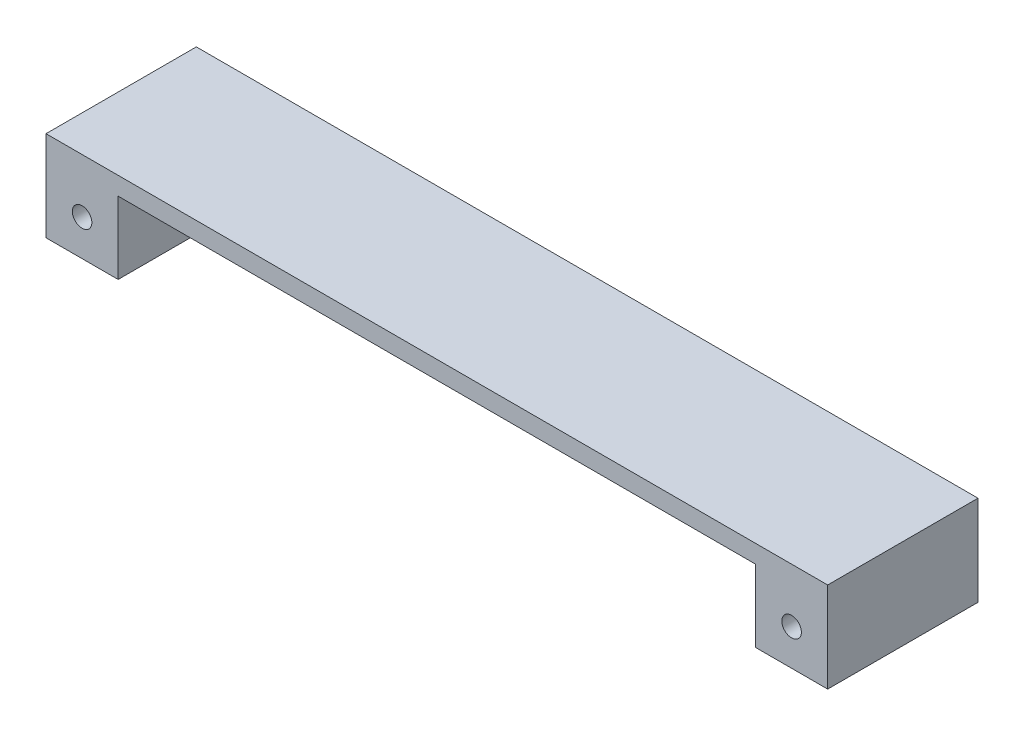
SolidWorks part; units mm, degrees
ref_plane "Front Plane" through (0, 0, 0) normal (0, 0, 1) x (1, 0, 0)
ref_plane "Top Plane" through (0, 0, 0) normal (0, 1, 0) x (1, 0, 0)
ref_plane "Right Plane" through (0, 0, 0) normal (1, 0, 0) x (0, 0, -1)
sketch "Sketch1" plane through (0, 0, 0) normal (0, 1, 0) x (1, 0, 0)
  line L1 (0, 0) -> (130, 0)
  line L2 (0, 0) -> (0, 25)
  line L3 (0, 25) -> (130, 25)
  line L4 (130, 0) -> (130, 25)
  dimension "D1" = 130
  dimension "D2" = 25
extrude "Boss-Extrude1" add sketch "Sketch1" along normal blind 3
sketch "Sketch2" plane through (0, 0, 0) normal (0, -1, 0) x (1, 0, 0)
  line L0 (65, 0) -> (65, -25) construction
  line L1 (0, 0) -> (12, 0)
  line L2 (0, 0) -> (0, -25)
  line L3 (0, -25) -> (12, -25)
  line L4 (12, 0) -> (12, -25)
  line L5 (0, 0) -> (130, 0) construction
  line L6 (130, -25) -> (0, -25) construction
  line L7 (130, -25) -> (118, -25)
  line L8 (118, 0) -> (118, -25)
  line L9 (130, 0) -> (118, 0)
  line L10 (130, 0) -> (130, -25)
  line L11 (0, -12.5) -> (130, -12.5) construction
  line L12 (0, -25) -> (0, 0) construction
  line L13 (130, 0) -> (130, -25) construction
  dimension "D1" = 25
  dimension "D2" = 12
extrude "Boss-Extrude2" add sketch "Sketch2" along normal blind 12
sketch "Sketch4" plane through (0, 0, 0) normal (0, 0, 1) x (1, 0, 0)
  line L0 (12, -12) -> (12, 0) construction
  line L1 (12, -12) -> (0, -12) construction
  line L2 (65, 3) -> (65, 0) construction
  line L3 (0, 3) -> (130, 3) construction
  line L4 (12, 0) -> (118, 0) construction
  circle A0 centre (6, -6) radius 1.625
  circle A1 centre (124, -6) radius 1.625
  dimension "D1" = 3.25
  dimension "D2" = 6
  dimension "D3" = 6
extrude "Cut-Extrude1" cut sketch "Sketch4" against normal through all
